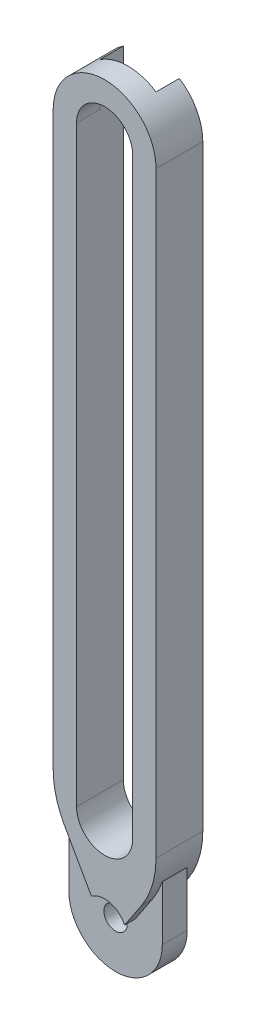
SolidWorks part; units mm, degrees
ref_plane "Piano frontale" through (0, 0, 0) normal (0, 0, 1) x (1, 0, 0)
ref_plane "Piano superiore" through (0, 0, 0) normal (0, 1, 0) x (1, 0, 0)
ref_plane "Piano destro" through (0, 0, 0) normal (1, 0, 0) x (0, 0, -1)
sketch "Schizzo1" plane through (0, 0, 0) normal (0, 0, 1) x (1, 0, 0)
  line L0 (0, -86.6264) -> (0, 113.3736) construction
  line L1 (-16.5, -86.6264) -> (-16.5, 113.3736)
  line L2 (16.5, -86.6264) -> (16.5, 113.3736)
  arc A0 (-16.5, -86.6264) -> (16.5, -86.6264) centre (0, -86.6264) ccw
  arc A1 (16.5, 113.3736) -> (-16.5, 113.3736) centre (0, 113.3736) ccw
  point P2 (0, 13.3736)
  dimension "D1" = 33
  dimension "D2" = 200
extrude "Estrusione-Estrusione1" add sketch "Schizzo1" along normal mid plane 15
sketch "Schizzo2" plane through (0, 0, 0) normal (0, 0, 1) x (1, 0, 0)
  line L0 (0, -88.7045) -> (0, -104.7045) construction
  line L1 (15, -88.7045) -> (15, -104.7045)
  line L2 (-15, -88.7045) -> (-15, -104.7045)
  line L3 (16.5, -86.6264) -> (-16.5, -86.6264) construction
  arc A0 (15, -88.7045) -> (-15, -88.7045) centre (0, -88.7045) ccw
  arc A1 (-15, -104.7045) -> (15, -104.7045) centre (0, -104.7045) ccw
  point P3 (0, -96.7045)
  dimension "D1" = 15
  dimension "D2" = 16
extrude "Estrusione-Estrusione2" add sketch "Schizzo2" along normal mid plane 8
sketch "Schizzo3" plane through (0, 0, 4) normal (0, 0, 1) x (1, 0, 0)
  line L0 (0, -104.7045) -> (15, -104.7045) construction
  line L1 (-4.2244, -99.1229) -> (-16.5, -77.3405)
  line L2 (-16.5, 113.3736) -> (-16.5, -86.6264) construction
  line L3 (-16.5, -77.3405) -> (-21.5105, -95.8261)
  line L4 (-21.5105, -95.8261) -> (-6.0799, -108.1737)
  line L5 (6.3871, -101.8401) -> (16.5, -86.6264)
  line L6 (16.5, -86.6264) -> (21.2626, -91.5332)
  line L7 (21.2626, -91.5332) -> (6.9988, -104.5751)
  arc A0 (-6.0799, -108.1737) -> (6.9988, -104.5751) centre (0, -104.7045) ccw
  arc A1 (6.3871, -101.8401) -> (-4.2244, -99.1229) centre (0, -104.7045) ccw
  arc A2 (-15, -93.5003) -> (15, -93.5003) centre (0, -86.6264) ccw construction
  point P12 (-21.5105, -95.8261)
  dimension "D1" = 14
extrude "Taglio-Estrusione1" cut sketch "Schizzo3" along normal blind 4
mirror "Specchia1" about plane through (0, 0, 0) normal (0, 0, 1) of "Taglio-Estrusione1"
sketch "Schizzo4" plane through (0, 0, 4) normal (0, 0, 1) x (1, 0, 0)
  line L0 (-15, -93.5003) -> (-15, -80.0022)
  line L1 (-4.2244, -99.1229) -> (-16.5, -77.3405) construction
  line L2 (-15, -80.0022) -> (-16.5, -77.3405)
  line L3 (-16.5, -77.3405) -> (-16.5, -93.5003)
  line L4 (-16.5, -93.5003) -> (-15, -93.5003)
  line L5 (15, -93.5003) -> (15, -88.883)
  line L6 (6.3871, -101.8401) -> (16.5, -86.6264) construction
  line L7 (15, -88.883) -> (16.5, -86.6264)
  line L8 (16.5, -86.6264) -> (16.5, -93.5003)
  line L9 (16.5, -93.5003) -> (15, -93.5003)
extrude "Taglio-Estrusione2" cut sketch "Schizzo4" against normal blind 8
fillet "Raccordo1" radius 28 2 edges at (-16.5, -77.3405, 0) (16.5, -86.6264, 0)
sketch "Schizzo9" plane through (0, 0, 4) normal (0, 0, 1) x (1, 0, 0)
  line L0 (0, -104.7045) -> (15, -104.7045) construction
hole_wizard "Foro per Vite M6.5-1" positions "Schizzo3D4" profile "Schizzo10" hole size "M6.5" standard "ISO"
sketch3d "Schizzo3D4"
  point P0 (0, -104.7045, 4)
sketch "Schizzo10" plane through (0, -104.7045, 4) normal (1, 0, 0) x (0, -1, 0)
  line L0 (0, 0) -> (0, 10.2532)
  line L1 (0, 10.2532) -> (3.75, 8)
  line L2 (3.75, 8) -> (3.75, 0)
  line L5 (3.75, 0) -> (0, 0)
  line L10 (0, 10.2532) -> (-3.75, 8) construction
  line L11 (0, -6.35) -> (0, 107.95) construction
  dimension "Hole Dia." = 7.5
  dimension "Hole Depth" = 8
  dimension "Drill Angle" = 118
sketch "Schizzo11" plane through (0, 0, 7.5) normal (0, 0, 1) x (1, 0, 0)
  line L0 (0, 113.3736) -> (0, -76.6264) construction
  line L1 (9, 113.3736) -> (9, -76.6264)
  line L2 (-9, 113.3736) -> (-9, -76.6264)
  arc A0 (9, 113.3736) -> (-9, 113.3736) centre (0, 113.3736) ccw
  arc A1 (-9, -76.6264) -> (9, -76.6264) centre (0, -76.6264) ccw
  point P4 (0, 18.3736)
  dimension "D1" = 9
  dimension "D2" = 190
extrude "Taglio-Estrusione3" cut sketch "Schizzo11" against normal through all
sketch "Schizzo13" plane through (0, 0, -7.5) normal (0, 0, -1) x (-1, 0, 0)
  line L0 (0, 113.3736) -> (0, 158.8684) construction
  line L1 (-9, 113.3736) -> (-9, 158.8684)
  line L2 (9, 113.3736) -> (9, 158.8684)
  line L3 (-9, -76.6264) -> (-9, 113.3736) construction
  arc A0 (-9, 113.3736) -> (9, 113.3736) centre (0, 113.3736) ccw
  arc A1 (9, 158.8684) -> (-9, 158.8684) centre (0, 158.8684) ccw
  point P4 (0, 136.121)
extrude "Taglio-Estrusione4" cut sketch "Schizzo13" against normal blind 7.5
sketch "Schizzo14" plane through (0, 0, 4) normal (0, 0, 1) x (1, 0, 0)
sketch "Schizzo15" plane through (16.5, 0, 0) normal (1, 0, 0) x (0, 0, -1)
  line L0 (7.5, 17.6022) -> (-7.5, 17.6022)
  line L1 (7.5, -78.1692) -> (7.5, 113.3736) construction
  line L2 (-7.5, -78.1692) -> (-7.5, 113.3736) construction
equation "\"80ù\"=90"
